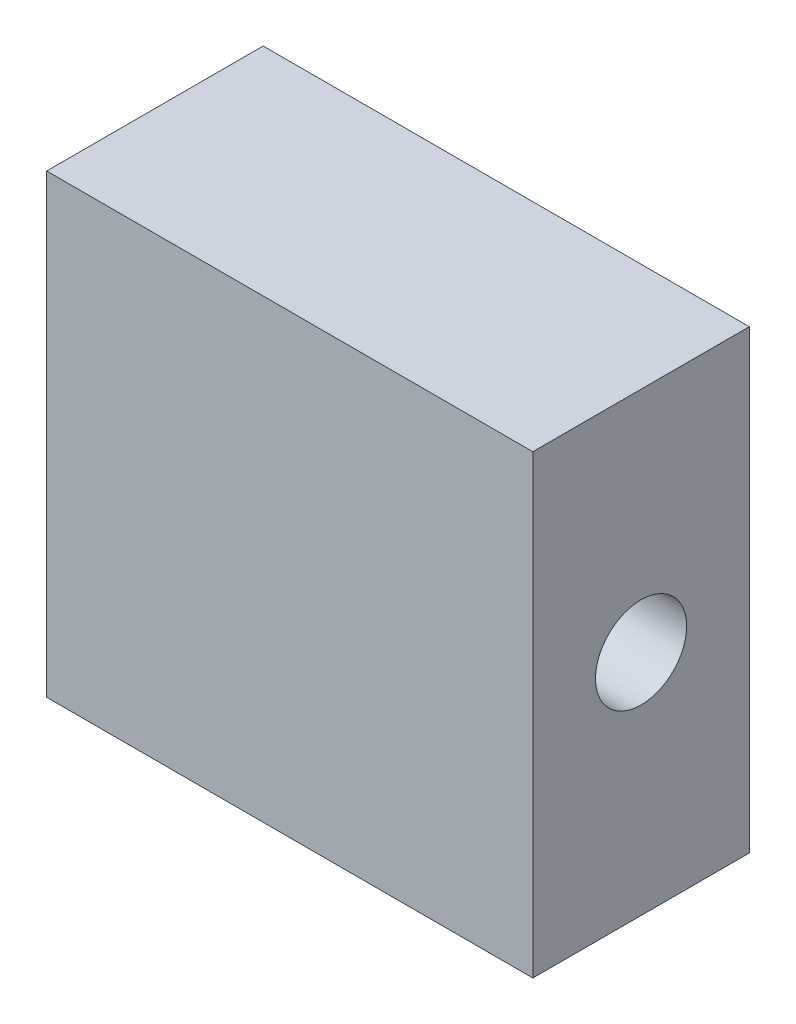
SolidWorks part; units mm, degrees
ref_plane "Front Plane" through (0, 0, 0) normal (0, 0, 1) x (1, 0, 0)
ref_plane "Top Plane" through (0, 0, 0) normal (0, 1, 0) x (1, 0, 0)
ref_plane "Right Plane" through (0, 0, 0) normal (1, 0, 0) x (0, 0, -1)
sketch "Sketch1" plane through (0, 0, 0) normal (0, 0, 1) x (1, 0, 0)
  line L1 (-16, -15) -> (16, -15)
  line L2 (-16, -15) -> (-16, 15)
  line L3 (-16, 15) -> (16, 15)
  line L4 (16, -15) -> (16, 15)
  line L5 (-16, -15) -> (16, 15) construction
  line L6 (-16, 15) -> (16, -15) construction
  point P0 (0, 0)
  point P5 (-10.6667, 10)
  point P6 (-10.6667, -10)
  point P8 (9.3333, -10)
  point P10 (9.3333, 10)
  dimension "D1" = 32
  dimension "D2" = 30
  dimension "D3" = 20
  dimension "D4" = 20
extrude "Boss-Extrude1" add sketch "Sketch1" along normal mid plane 14.25
hole_wizard "M3x0.5 Tapped Hole1" positions "Sketch2" profile "Sketch4" tap size "M3x0.5" standard "ANSI Metric"
sketch "Sketch2" plane through (0, 0, -7.125) normal (0, 0, -1) x (-1, 0, 0)
  point P0 (-9.3333, 10)
  point P3 (10.6667, 10)
  point P6 (10.6667, -10)
  point P9 (-9.3333, -10)
sketch "Sketch4" plane through (9.3333, 10, -7.125) normal (1, 0, 0) x (0, 1, 0)
  line L0 (0, 0) -> (0, 8.2511)
  line L1 (0, 8.2511) -> (1.25, 7.5)
  line L2 (1.25, 7.5) -> (1.25, 0)
  line L5 (1.25, 0) -> (0, 0)
  line L10 (0, 8.2511) -> (-1.25, 7.5) construction
  line L11 (0, -6.35) -> (0, 107.95) construction
  dimension "Tap Drill Dia." = 2.5
  dimension "Tap Drill Depth" = 7.5
  dimension "Drill Angle" = 118
hole_wizard "M6x1.0 Tapped Hole1" positions "Sketch6" profile "Sketch7" tap size "M6x1.0" standard "ANSI Metric" end condition through all
sketch "Sketch6" plane through (16, 0, 0) normal (1, 0, 0) x (0, 0, -1)
  point P0 (0, 0)
sketch "Sketch7" plane through (16, 0, 0) normal (0, 1, 0) x (0, 0, -1)
  line L0 (0, 0) -> (0, 32)
  line L1 (0, 32) -> (3, 32)
  line L2 (3, 32) -> (3, 0)
  line L5 (3, 0) -> (0, 0)
  line L11 (0, -6.35) -> (0, 107.95) construction
  dimension "Thread Major Dia." = 6
  dimension "Thru Tap Drill Depth" = 32
